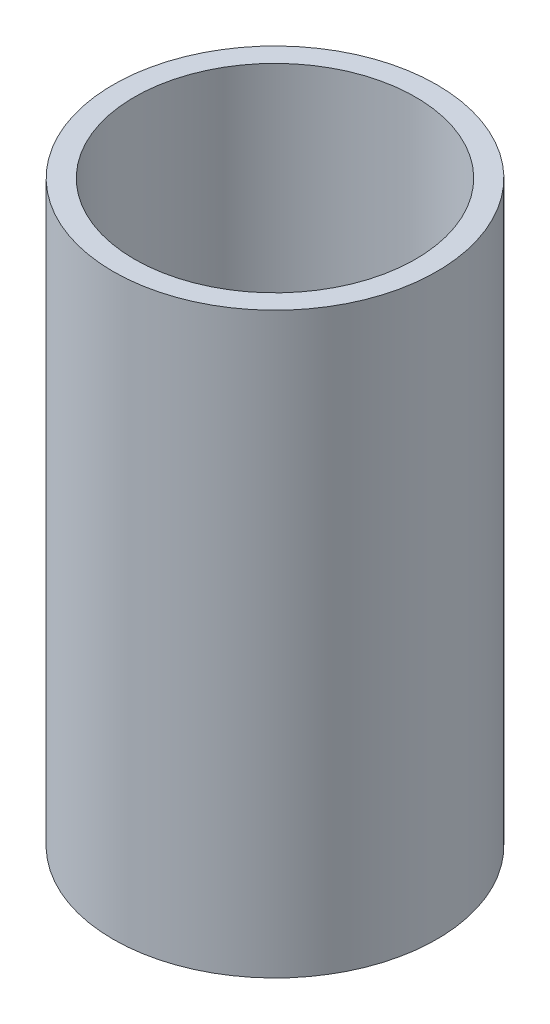
SolidWorks part; units mm, degrees
ref_plane "Front Plane" through (0, 0, 0) normal (0, 0, 1) x (1, 0, 0)
ref_plane "Top Plane" through (0, 0, 0) normal (0, 1, 0) x (1, 0, 0)
ref_plane "Right Plane" through (0, 0, 0) normal (1, 0, 0) x (0, 0, -1)
sketch "Sketch1" plane through (0, 0, 0) normal (0, 1, 0) x (1, 0, 0)
  circle A0 centre (0, 0) radius 40
  dimension "SLEEVE_OD" = 80
extrude "Boss-Extrude1" add sketch "Sketch1" along normal blind 142.9391
sketch "Sketch2" plane through (0, 0, 0) normal (0, 1, 0) x (1, 0, 0)
  circle A0 centre (0, 0) radius 34.7363
  dimension "BORE_D" = 69.4726
extrude "Cut-Extrude1" cut sketch "Sketch2" along normal through all
chamfer "Chamfer1" distance 3.3204 angle 45 rebuild error yes
